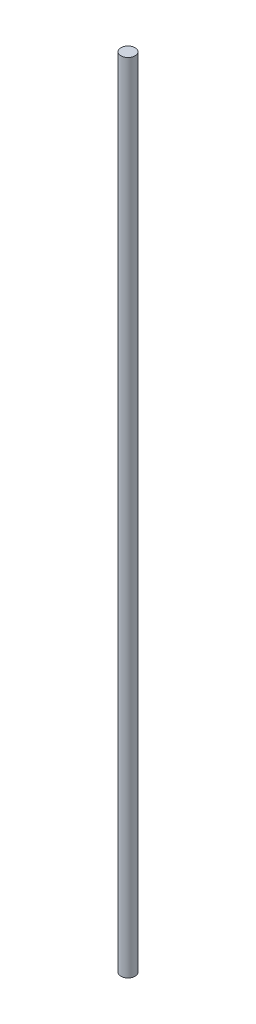
SolidWorks part; units mm, degrees
material "AISI 1020"
ref_plane "Front Plane" through (0, 0, 0) normal (0, 0, 1) x (1, 0, 0)
ref_plane "Top Plane" through (0, 0, 0) normal (0, 1, 0) x (1, 0, 0)
ref_plane "Right Plane" through (0, 0, 0) normal (1, 0, 0) x (0, 0, -1)
sketch "Sketch1" plane through (0, 0, 0) normal (0, 1, 0) x (1, 0, 0)
  circle A0 centre (0, 0) radius 3
  dimension "D1" = 6
extrude "Boss-Extrude1" add sketch "Sketch1" along normal blind 170 and the other way blind 170
cosmetic thread "Cosmetic Thread1" parameters "D2"=4.891
